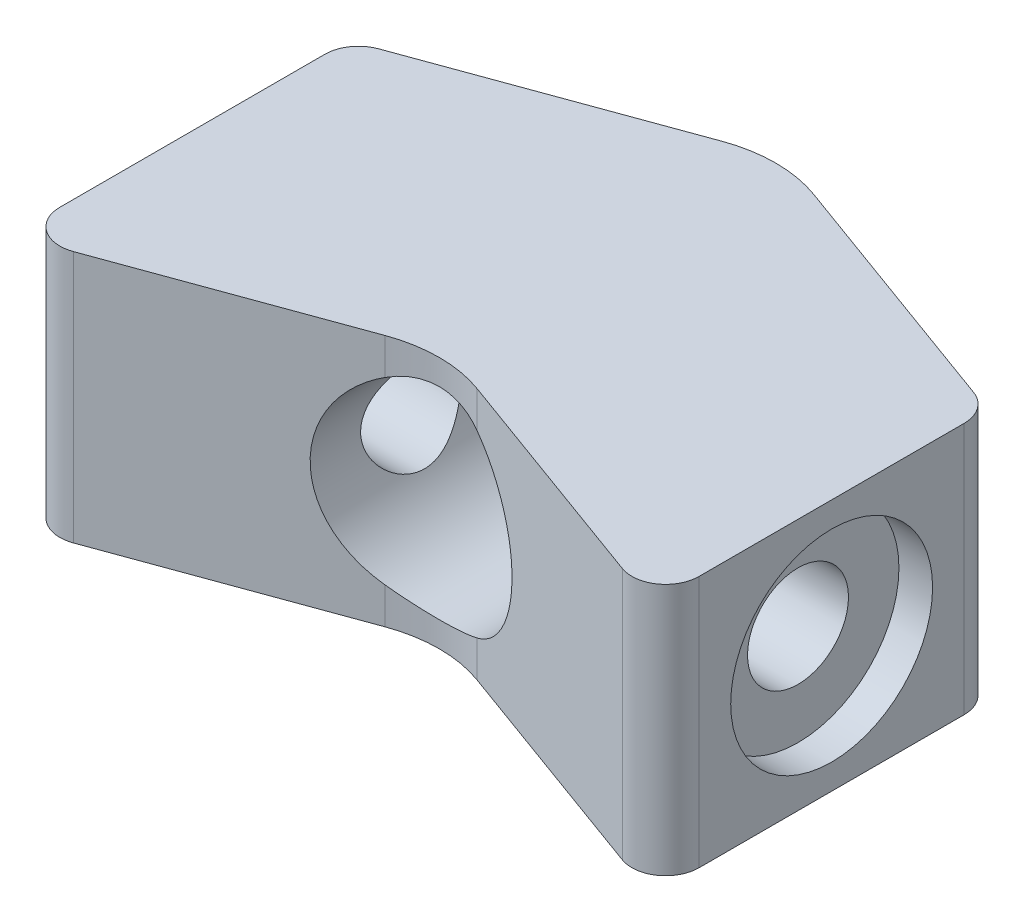
SolidWorks part; units mm, degrees
ref_plane "前视基准面" through (0, 0, 0) normal (0, 0, 1) x (1, 0, 0)
ref_plane "上视基准面" through (0, 0, 0) normal (0, 1, 0) x (1, 0, 0)
ref_plane "右视基准面" through (0, 0, 0) normal (1, 0, 0) x (0, 0, -1)
sketch "草图1" plane through (0, 0, 0) normal (0, 1, 0) x (1, 0, 0)
  line L6 (-2.7362, 7.5175) -> (-17.684, 2.077)
  line L7 (-19, 0.1976) -> (-19, -15.5523)
  line L8 (0, 27.5112) -> (0, -65.8277) construction
  line L9 (-16.316, -17.4316) -> (-2.7362, -12.489)
  line L10 (16.316, -17.4316) -> (2.7362, -12.489)
  line L11 (19, 0.1976) -> (19, -15.5523)
  line L12 (2.7362, 7.5175) -> (17.684, 2.077)
  arc A1 (2.7362, 7.5175) -> (-2.7362, 7.5175) centre (0, 0) ccw
  arc A4 (2.7362, -12.489) -> (-2.7362, -12.489) centre (0, -20.0065) ccw
  arc A5 (-17.684, 2.077) -> (-19, 0.1976) centre (-17, 0.1976) ccw
  arc A6 (-19, -15.5523) -> (-16.316, -17.4316) centre (-17, -15.5523) ccw
  arc A12 (19, -15.5523) -> (16.316, -17.4316) centre (17, -15.5523) cw
  arc A13 (17.684, 2.077) -> (19, 0.1976) centre (17, 0.1976) cw
  dimension "D2" = 2
  dimension "D1" = 140
  dimension "D3" = 8
  dimension "D4" = 8
  dimension "D5" = 2
  dimension "D7" = 18.8
  dimension "D6" = 38
extrude "凸台-拉伸1" add sketch "草图1" along normal blind 15
sketch "草图2" plane through (0, 0, 0) normal (0, 0, 1) x (1, 0, 0)
  line L0 (0, 21.6362) -> (0, -11.4793) construction
  line L1 (-17.684, 15) -> (-17.684, 0) construction
  line L2 (-17.684, 7.5) -> (24.9191, 7.5) construction
  circle A0 centre (0, 7.5) radius 6
extrude "切除-拉伸1" cut sketch "草图2" along normal through all and the other way blind 15
sketch "草图4" plane through (-19, 0, 0) normal (-1, 0, 0) x (0, 0, 1)
  line L0 (7.6773, 25.4215) -> (7.6773, -16.4241) construction
  line L1 (23.7942, 7.5) -> (-17.9359, 7.5) construction
  circle A0 centre (7.6773, 7.5) radius 3
  circle A1 centre (7.6773, 7.5) radius 6
extrude "切除-拉伸4" cut sketch "草图4" against normal blind 20 contours A0 region at (-19, 7.5, 7.6773)
extrude "切除-拉伸5" cut sketch "草图4<5>" against normal blind 2 contours A1 A0 region at (-19, 7.5, 1.847)
sketch "草图4<5>" plane through (-19, 0, 0) normal (-1, 0, 0) x (0, 0, 1) same geometry as "草图4"
mirror "镜向1" about plane through (0, 0, 0) normal (1, 0, 0) of "切除-拉伸4", "切除-拉伸5"
